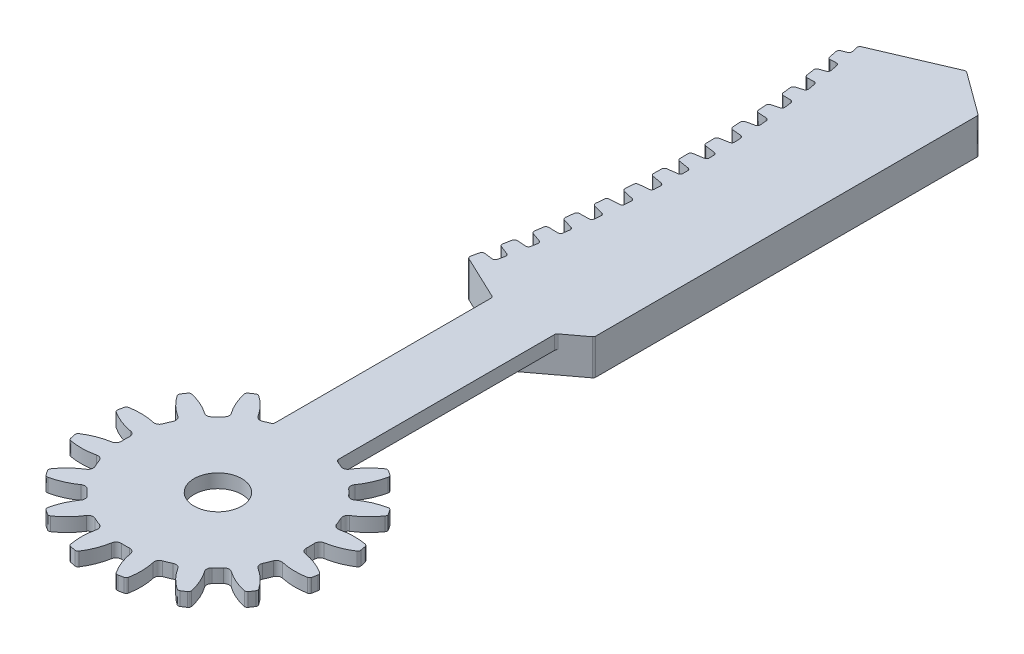
SolidWorks part; units mm, degrees
ref_plane "Front Plane" through (0, 0, 0) normal (0, 0, 1) x (1, 0, 0)
ref_plane "Top Plane" through (0, 0, 0) normal (0, 1, 0) x (1, 0, 0)
ref_plane "Right Plane" through (0, 0, 0) normal (1, 0, 0) x (0, 0, -1)
sketch "Sketch1" plane through (0, 0, 0) normal (0, 1, 0) x (1, 0, 0)
  circle A0 centre (0, 0) radius 22.5
  circle A1 centre (0, 0) radius 4.35
  dimension "D1" = 45
  dimension "D2" = 8.7
extrude "Boss-Extrude1" add sketch "Sketch1" along normal blind 2.5
sketch "Sketch3" plane through (0, 2.5, 0) normal (0, 1, 0) x (1, 0, 0)
  line L0 (0, -1.375) -> (0, 1.375) construction
  line L1 (0, 0) -> (-1.6059, 16.7984) construction
  line L2 (0, 13.4609) -> (-4.1306, 24.8095) construction
  arc A0 (2.3332, 19.8634) -> (-2.3332, 19.8634) centre (0, 0) ccw construction
  arc A1 (1.6059, 16.7984) -> (-1.6059, 16.7984) centre (0, 0) ccw
  circle A2 centre (0, 0) radius 22.5 construction
  arc A3 (-3.577, 22.2139) -> (-1.6059, 16.7984) centre (-13.032, 15.7061) cw
  arc A4 (3.577, 22.2139) -> (1.6059, 16.7984) centre (13.032, 15.7061) ccw
  arc A5 (-3.577, 22.2139) -> (3.577, 22.2139) centre (0, 0) cw
  point P27 (-2.246, 19.6318)
  dimension "D1" = 40
  dimension "D2" = 5.625
  dimension "D3" = 20
  dimension "D4" = 4.677
extrude "Cut-Extrude2" cut sketch "Sketch3" against normal through all
fillet "Fillet1" radius 0.95 2 edges at (-1.6059, 1.25, -16.7984) (1.6059, 1.25, -16.7984)
fillet "Fillet2" radius 0.5 2 edges at (3.577, 1.25, -22.2139) (-3.577, 1.25, -22.2139)
pattern_circular "CirPattern1" count 16 over 360 about axis through (0, 2.5, 0) along (0, 1, 0) of "Cut-Extrude2", "Fillet1", "Fillet2"
sketch "Sketch4" plane through (0, 0, 0) normal (0, 1, 0) x (1, 0, 0)
  line L0 (-5.7669, 15.859) -> (-5.7669, 55.859)
  line L1 (5.7669, 15.859) -> (5.7669, 55.859)
  line L2 (-12.0914, 58.859) -> (-5.7669, 55.859)
  line L3 (5.7669, 55.859) -> (9.7669, 58.859)
  line L4 (9.7669, 58.859) -> (9.7669, 128.859)
  line L5 (9.7669, 128.859) -> (1.697, 134.7648)
  line L6 (1.697, 134.7648) -> (-12.0914, 128.859)
  line L8 (-5.7669, 15.859) -> (5.7669, 15.859)
  line L9 (-5.7669, 55.859) -> (1.2984, 52.5077)
  line L10 (1.2984, 52.5077) -> (5.7669, 55.859)
  arc A0 (-12.0914, 128.859) -> (-12.0914, 58.859) centre (-157.9509, 93.859) cw
  point P31 (-7.9509, 93.859)
  point P32 (9.7669, 93.859)
  dimension "D2" = 70
  dimension "D3" = 150
  dimension "D1" = 40
  dimension "D4" = 7
  dimension "D5" = 70
  dimension "D6" = 5
  dimension "D7" = 15
  dimension "D8" = 10
  dimension "D9" = 3
extrude "Boss-Extrude3" add sketch "Sketch4" along normal up to surface (2.5 mm away) contours L10 L9 L0 L8 L1 region at (-0.0189, 0, -35.0334) up to face at (0, 2.5, 4.35)
extrude "Boss-Extrude4" add sketch "Sketch4<3>" along normal blind 2.5 and the other way blind 4 contours L6 A0 L2 L9 L10 L3 L4 L5 region at (0.1401, 0, -93.7296)
sketch "Sketch4<3>" plane through (0, 0, 0) normal (0, 1, 0) x (1, 0, 0) same geometry as "Sketch4"
fillet "Fillet5" radius 0.5 8 edges at (1.697, -0.75, -134.7648) (9.7669, -0.75, -128.859) (5.7669, 1.25, -55.859) (9.7669, -0.75, -58.859) (5.7669, 1.25, -15.859) (-5.7669, 1.25, -15.859) (-5.7669, 1.25, -55.859) (1.2984, -2, -52.5077)
sketch "Sketch6" plane through (0, 0, 0) normal (0, 1, 0) x (1, 0, 0)
  line L0 (-12.0914, 128.859) -> (-14.3895, 127.8747)
  line L1 (-14.3502, 59.9305) -> (-12.0914, 58.859)
  line L2 (1.435, 134.6525) -> (-12.0914, 128.859) construction
  line L3 (-12.0914, 58.859) -> (-6.0526, 55.9946) construction
  line L6 (-1010.6112, 95.5891) -> (48989.3888, 95.5891) construction
  line L8 (-10.3916, 124.268) -> (-12.9258, 124.1075)
  line L10 (-13.3401, 126.3735) -> (-10.9795, 127.3092)
  line L12 (-9.5593, 119.2262) -> (-12.142, 119.1648)
  line L14 (-12.483, 121.4429) -> (-10.0456, 122.2995)
  line L16 (-8.8992, 114.1587) -> (-11.5182, 114.1993)
  line L18 (-11.7854, 116.4873) -> (-9.282, 117.258)
  line L20 (-8.4121, 109.0718) -> (-11.055, 109.2163)
  line L22 (-11.2482, 111.5117) -> (-8.69, 112.191)
  line L24 (-8.0985, 103.9717) -> (-10.7529, 104.2209)
  line L26 (-10.8719, 106.5213) -> (-8.2705, 107.1046)
  line L28 (-7.9589, 98.8646) -> (-10.6122, 99.2183)
  line L29 (-7.9873, 97.1598) -> (-10.6287, 96.7407)
  line L30 (-10.6569, 101.5215) -> (-8.0242, 102.005)
  line L31 (-10.6023, 94.4373) -> (-7.951, 94.0181)
  line L33 (-7.9589, 92.3135) -> (-10.6122, 91.9598)
  line L35 (-10.6569, 89.6567) -> (-8.0242, 89.1732)
  line L37 (-8.0985, 87.2065) -> (-10.7529, 86.9573)
  line L39 (-10.8719, 84.6568) -> (-8.2705, 84.0736)
  line L41 (-8.4121, 82.1063) -> (-11.055, 81.9619)
  line L43 (-11.2482, 79.6665) -> (-8.69, 78.9871)
  line L44 (-8.8992, 77.0194) -> (-11.5182, 76.9789)
  line L45 (-11.7854, 74.6909) -> (-9.282, 73.9201)
  line L46 (-9.5593, 71.952) -> (-12.142, 72.0134)
  line L47 (-12.483, 69.7352) -> (-10.0456, 68.8787)
  line L49 (-10.3916, 66.9102) -> (-12.9258, 67.0706)
  line L51 (-13.3401, 64.8047) -> (-10.9795, 63.8689)
  line L53 (-11.4145, 61.8111) -> (-13.8743, 62.1295)
  arc A0 (-14.3895, 127.8747) -> (-13.9, 125.6238) centre (-165.6011, 93.8151) cw
  arc A1 (-12.0914, 58.859) -> (-11.4145, 61.8111) centre (-157.9509, 93.859) ccw
  arc A2 (-12.0914, 58.859) -> (-12.0914, 128.859) centre (-157.9509, 93.859) ccw construction
  arc A3 (-13.8743, 62.1295) -> (-14.3502, 59.9305) centre (-165.6011, 93.8151) cw
  arc A4 (-12.9258, 67.0706) -> (-13.3401, 64.8047) centre (-165.6011, 93.8151) cw
  arc A5 (-10.9795, 63.8689) -> (-10.3916, 66.9102) centre (-157.9509, 93.859) ccw
  arc A6 (-10.0456, 68.8787) -> (-9.5593, 71.952) centre (-157.9509, 93.859) ccw
  arc A7 (-12.142, 72.0134) -> (-12.483, 69.7352) centre (-165.6011, 93.8151) cw
  arc A8 (-9.282, 73.9201) -> (-8.8992, 77.0194) centre (-157.9509, 93.859) ccw
  arc A9 (-11.5182, 76.9789) -> (-11.7854, 74.6909) centre (-165.6011, 93.8151) cw
  arc A10 (-8.69, 78.9871) -> (-8.4121, 82.1063) centre (-157.9509, 93.859) ccw
  arc A11 (-11.055, 81.9619) -> (-11.2482, 79.6665) centre (-165.6011, 93.8151) cw
  arc A12 (-8.2705, 84.0736) -> (-8.0985, 87.2065) centre (-157.9509, 93.859) ccw
  arc A13 (-10.7529, 86.9573) -> (-10.8719, 84.6568) centre (-165.6011, 93.8151) cw
  arc A14 (-8.0242, 89.1732) -> (-7.9589, 92.3135) centre (-157.9509, 93.859) ccw
  arc A15 (-10.6122, 91.9598) -> (-10.6569, 89.6567) centre (-165.6011, 93.8151) cw
  arc A16 (-7.951, 94.0181) -> (-7.9873, 97.1598) centre (-157.9509, 93.859) ccw
  arc A17 (-10.6287, 96.7407) -> (-10.6023, 94.4373) centre (-165.6011, 93.8151) cw
  arc A30 (-11.4022, 125.8505) -> (-12.0914, 128.859) centre (-157.9509, 93.859) ccw
  arc A31 (-12.9258, 124.1075) -> (-13.3401, 126.3735) centre (-165.6011, 97.3631) ccw
  arc A32 (-10.9795, 127.3092) -> (-10.3916, 124.268) centre (-157.9509, 97.3191) cw
  arc A33 (-12.142, 119.1648) -> (-12.483, 121.4429) centre (-165.6011, 97.3631) ccw
  arc A34 (-10.0456, 122.2995) -> (-9.5593, 119.2262) centre (-157.9509, 97.3191) cw
  arc A35 (-11.5182, 114.1993) -> (-11.7854, 116.4873) centre (-165.6011, 97.3631) ccw
  arc A36 (-9.282, 117.258) -> (-8.8992, 114.1587) centre (-157.9509, 97.3191) cw
  arc A37 (-11.055, 109.2163) -> (-11.2482, 111.5117) centre (-165.6011, 97.3631) ccw
  arc A38 (-8.69, 112.191) -> (-8.4121, 109.0718) centre (-157.9509, 97.3191) cw
  arc A39 (-10.7529, 104.2209) -> (-10.8719, 106.5213) centre (-165.6011, 97.3631) ccw
  arc A40 (-8.2705, 107.1046) -> (-8.0985, 103.9717) centre (-157.9509, 97.3191) cw
  arc A41 (-10.6122, 99.2183) -> (-10.6569, 101.5215) centre (-165.6011, 97.3631) ccw
  arc A42 (-8.0242, 102.005) -> (-7.9589, 98.8646) centre (-157.9509, 97.3191) cw
  point P77 (-12.3083, 70.8737)
  point P78 (-11.6475, 75.8344)
  point P79 (-11.1473, 80.8138)
  point P80 (-10.8081, 85.8068)
  point P81 (-10.6302, 90.8082)
  point P82 (-10.6112, 95.5891)
  point P83 (-7.9609, 95.5891)
  point P84 (-13.1288, 65.9369)
  point P85 (-14.1082, 61.0291)
  dimension "D3" = 155
  dimension "D1" = 2.5
  dimension "D2" = 2.5
  dimension "D11" = 18
  dimension "D12" = 18
  dimension "D13" = 18
  dimension "D14" = 18
  dimension "D15" = 18
  dimension "D16" = 18
  dimension "D17" = 18
  dimension "D18" = 18
  dimension "D20" = 2.25
  dimension "D19" = 1.85
  dimension "D21" = 1.85
  dimension "D22" = 1.85
  dimension "D23" = 1.85
  dimension "D24" = 1.85
  dimension "D25" = 1.85
extrude "Boss-Extrude5" add sketch "Sketch6" along normal up to surface and the other way up to surface contours A32 L10 A31 L8 | A34 L14 A33 L12 | A36 L18 A35 L16 | A38 L22 A37 L20 | A40 L26 A39 L24 | A42 L30 A41 L28 | L33 A15 L35 A14 | L41 A11 L43 A10 | L44 A9 L45 A8 | L46 A7 L47 A6 | L51 A5 L49 A4 | L53 A3 L1 A1 | L31 A16 L29 A17 | L39 A12 L37 A13 region at (-12.87, 0, -60.667) region at (-11.8447, 0, -125.5266) region at (-10.9906, 0, -120.5436) region at (-10.3023, 0, -115.5341) region at (-9.7809, 0, -110.5038) region at (-9.427, 0, -105.4585) region at (-9.241, 0, -100.4038) region at (-9.241, 0, -90.7744) region at (-9.7809, 0, -80.6744) region at (-10.3023, 0, -75.6441) region at (-10.9906, 0, -70.6346) region at (-11.8447, 0, -65.6516) up to face at (0.172, 2.5, -6.3257) other way up to face at (2.4658, -4, -93.772)
fillet "Fillet6" radius 0.5 56 edges at (-12.0914, -0.75, -128.859) (-12.483, -0.75, -121.4429) (-11.6662, -0.75, -127.037) (-13.3401, -0.75, -126.3735) (-12.9258, -0.75, -124.1075) (-11.0569, -0.75, -124.2259) (-10.6322, -0.75, -122.0933) (-12.142, -0.75, -119.1648) (-10.1092, -0.75, -119.2131) (-9.7639, -0.75, -117.1097) (-11.7854, -0.75, -116.4873) (-11.5182, -0.75, -114.1993) (-9.3318, -0.75, -114.1654) (-9.0632, -0.75, -112.0919) (-11.2482, -0.75, -111.5117) (-11.055, -0.75, -109.2163) (-8.7261, -0.75, -109.089) (-8.5317, -0.75, -107.046) (-10.8719, -0.75, -106.5213) (-10.7529, -0.75, -104.2209) (-8.2935, -0.75, -103.99) (-8.1708, -0.75, -101.978) (-10.6569, -0.75, -101.5215) (-10.6122, -0.75, -99.2183) (-8.0348, -0.75, -98.8747) (-7.9873, -0.75, -97.1598) (-10.6287, -0.75, -96.7407) (-10.6023, -0.75, -94.4373) (-7.951, -0.75, -94.0181) (-7.9589, -0.75, -92.3135) (-10.6122, -0.75, -91.9598) (-10.6569, -0.75, -89.6567) (-8.0242, -0.75, -89.1732) (-8.0985, -0.75, -87.2065) (-10.7529, -0.75, -86.9573) (-10.8719, -0.75, -84.6568) (-8.2705, -0.75, -84.0736) (-8.4121, -0.75, -82.1063) (-11.055, -0.75, -81.9619) (-11.2482, -0.75, -79.6665) (-8.69, -0.75, -78.9871) (-8.8992, -0.75, -77.0194) (-11.5182, -0.75, -76.9789) (-11.7854, -0.75, -74.6909) (-9.282, -0.75, -73.9201) (-9.5593, -0.75, -71.952) (-12.142, -0.75, -72.0134) (-12.483, -0.75, -69.7352) (-10.0456, -0.75, -68.8787) (-10.3916, -0.75, -66.9102) (-12.9258, -0.75, -67.0706) (-13.3401, -0.75, -64.8047) (-10.9795, -0.75, -63.8689) (-11.4145, -0.75, -61.8111) (-13.8743, -0.75, -62.1295) (-14.3502, -0.75, -59.9305)
equation "\"N\"= 16"
equation "\"Module\"= \"outerD\" / ( \"N\" + 2 )"
equation "\"outerD\"= 45"
equation "\"pitchD\"= \"N\" * \"Module\""
equation "\"Backlash\"= 0.3 * \"Module\""
equation "\"ArcLength\"= ( ( \"Module\" * pi ) / 2 ) + \"Backlash\""
equation "\"FilletR\"= 0.38 * \"Module\""
equation "\"D1@Sketch3\"=\"pitchD\""
equation "\"toothdepth\"= 2.25 * \"Module\""
equation "\"D2@Sketch3\"=\"toothdepth\""
equation "\"D3@Sketch3\"=20"
equation "\"D4@Sketch3\"=\"ArcLength\""
equation "\"D1@Fillet1\"=\"FilletR\""
equation "\"D1@CirPattern1\"=\"N\""
equation "\"D21@Sketch6\"=\"D19@Sketch6\""
equation "\"D22@Sketch6\"=\"D19@Sketch6\""
equation "\"D23@Sketch6\"=\"D19@Sketch6\""
equation "\"D24@Sketch6\"=\"D19@Sketch6\""
equation "\"D25@Sketch6\"=\"D19@Sketch6\""
